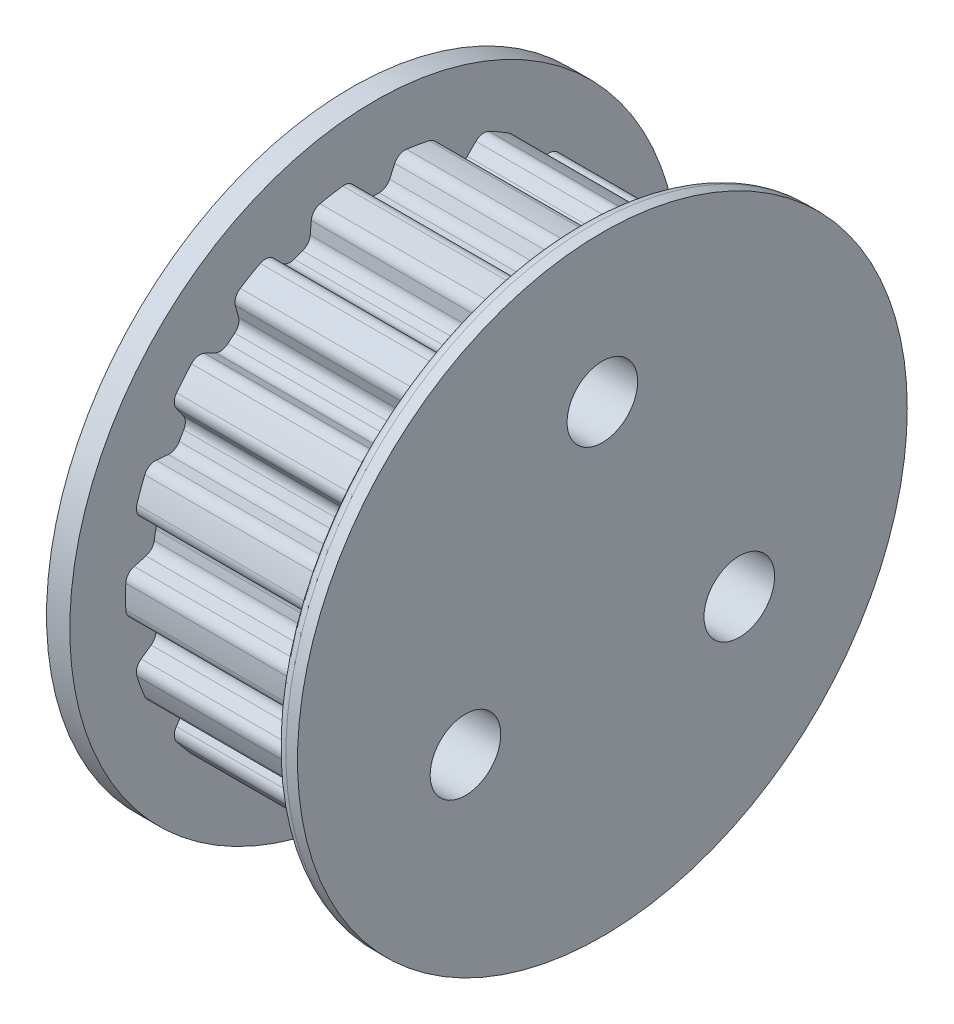
SolidWorks part; units mm, degrees
ref_plane "Front Plane" through (0, 0, 0) normal (0, 0, 1) x (1, 0, 0)
ref_plane "Top Plane" through (0, 0, 0) normal (0, 1, 0) x (1, 0, 0)
ref_plane "Right Plane" through (0, 0, 0) normal (1, 0, 0) x (0, 0, -1)
sketch "Sketch3" plane through (0, 0, 0) normal (1, 0, 0) x (0, 0, -1)
  circle A0 centre (0, 0) radius 13.4031
  dimension "D1" = 26.8063
extrude "Boss-Extrude1" add sketch "Sketch3" along normal mid plane 11
sketch "Sketch4" plane through (0, 0, 0) normal (1, 0, 0) x (0, 0, -1)
  line L0 (0, 0) -> (0, 21.2108) construction
  line L1 (-1.2677, 13.343) -> (-0.635, 11.9863)
  line L2 (1.2677, 13.343) -> (0.635, 11.9863)
  circle A0 centre (0, 0) radius 13.4031 construction
  circle A1 centre (0, 0) radius 13.4031 construction
  circle A2 centre (0, 0) radius 12.0031 construction
  arc A3 (-0.635, 11.9863) -> (0.635, 11.9863) centre (0, 0) cw
  arc A4 (-1.2677, 13.343) -> (1.2677, 13.343) centre (0, 0) cw
  dimension "D1" = 1.4
  dimension "D2" = 1.27
  dimension "D3" = 25
extrude "Cut-Extrude1" cut sketch "Sketch4" against normal mid plane 11
fillet "Fillet1" radius 0.61 4 edges at (0, 13.343, -1.2677) (0, 13.343, 1.2677) (0, 11.9863, -0.635) (0, 11.9863, 0.635)
pattern_circular "CirPattern1" count 18 over 360 about axis through (5.5, 0, 0) along (1, 0, 0) of "Cut-Extrude1", "Fillet1"
sketch "Sketch8" plane through (0, 0, 0) normal (1, 0, 0) x (0, 0, -1)
  circle A0 centre (0, 0) radius 16.4031
  dimension "D1" = 32.8063
extrude "Boss-Extrude4" add sketch "Sketch8" along normal blind 1.25 from surface starting at face at (5.5, 0, 0)
extrude "Boss-Extrude5" add sketch "Sketch8<2>" against normal blind 1.25 from surface starting at face at (-5.5, 0, 0)
sketch "Sketch8<2>" plane through (0, 0, 0) normal (1, 0, 0) x (0, 0, -1) same geometry as "Sketch8"
fillet "Fillet2" radius 0.625 1 edges at (5.5, 0, -16.4031)
sketch "Sketch9" plane through (-6.75, 0, 0) normal (-1, 0, 0) x (0, 0, 1)
  circle A2 centre (0, 0) radius 9.4031
  circle A3 centre (0, 0) radius 9.4031
  dimension "D1" = 7
extrude "Cut-Extrude2" [suppressed] cut sketch "Sketch9" against normal up to next
sketch "Sketch10" plane through (-6.75, 0, 0) normal (-1, 0, 0) x (0, 0, 1)
  line L0 (0, 8.5055) -> (-7.366, -4.2528) construction
  line L1 (-7.366, -4.2528) -> (7.366, -4.2528) construction
  line L2 (7.366, -4.2528) -> (0, 8.5055) construction
  line L3 (0, 8.5055) -> (0, 0) construction
  line L4 (0, 0) -> (-7.366, -4.2528) construction
  line L7 (7.366, -4.2528) -> (0, 0) construction
  circle A0 centre (0, 0) radius 6.35
  dimension "D1" = 14.732
  dimension "D2" = 12.7
extrude "Cut-Extrude3" cut sketch "Sketch10" against normal blind 3.175
hole_wizard "#6 Clearance Hole1" positions "Sketch11" profile "Sketch12" hole size "#6" standard "ANSI Inch" end condition up to next
sketch "Sketch11" plane through (-6.75, 0, 0) normal (-1, 0, 0) x (0, 0, 1)
  point P0 (0, 8.5055)
  point P3 (-7.366, -4.2528)
  point P6 (7.366, -4.2528)
sketch "Sketch12" plane through (-6.75, 8.5055, 0) normal (0, 1, 0) x (0, 0, 1)
  line L0 (0, 0) -> (0, 13.5)
  line L1 (0, 13.5) -> (1.8986, 13.5)
  line L2 (1.8986, 13.5) -> (1.8986, 0)
  line L5 (1.8986, 0) -> (0, 0)
  line L11 (0, -6.35) -> (0, 107.95) construction
  dimension "Thru Hole Dia." = 3.7973
  dimension "Thru Hole Depth" = 13.5
sketch "Sketch13" [suppressed] plane through (-6.75, 0, 0) normal (-1, 0, 0) x (0, 0, 1)
  line L1 (5.4993, 0) -> (2.7496, 4.7625)
  line L2 (2.7496, 4.7625) -> (-2.7496, 4.7625)
  line L3 (-2.7496, 4.7625) -> (-5.4993, 0)
  line L4 (-5.4993, 0) -> (-2.7496, -4.7625)
  line L5 (-2.7496, -4.7625) -> (2.7496, -4.7625)
  line L6 (2.7496, -4.7625) -> (5.4993, 0)
  circle A0 centre (0, 0) radius 4.7625 construction
  dimension "D1" = 9.525
extrude "Cut-Extrude4" [suppressed] cut sketch "Sketch13" against normal up to next
sketch "Sketch15" [suppressed] plane through (5.5, 0, 0) normal (1, 0, 0) x (0, 0, -1)
  circle A0 centre (0, 0) radius 1.5875
  point P0 (0, 0)
  dimension "D1" = 3.175
extrude "Cut-Extrude7" [suppressed] cut sketch "Sketch15" against normal up to next
equation "\"n\" =18"
equation "\"D1@CirPattern1\"=\"n\""
equation "\"D1@Sketch3\"=\"n\" * 5.08 / pi-2.3"
equation "\"D1@Sketch8\"=\"D1@Sketch3\"+6"
